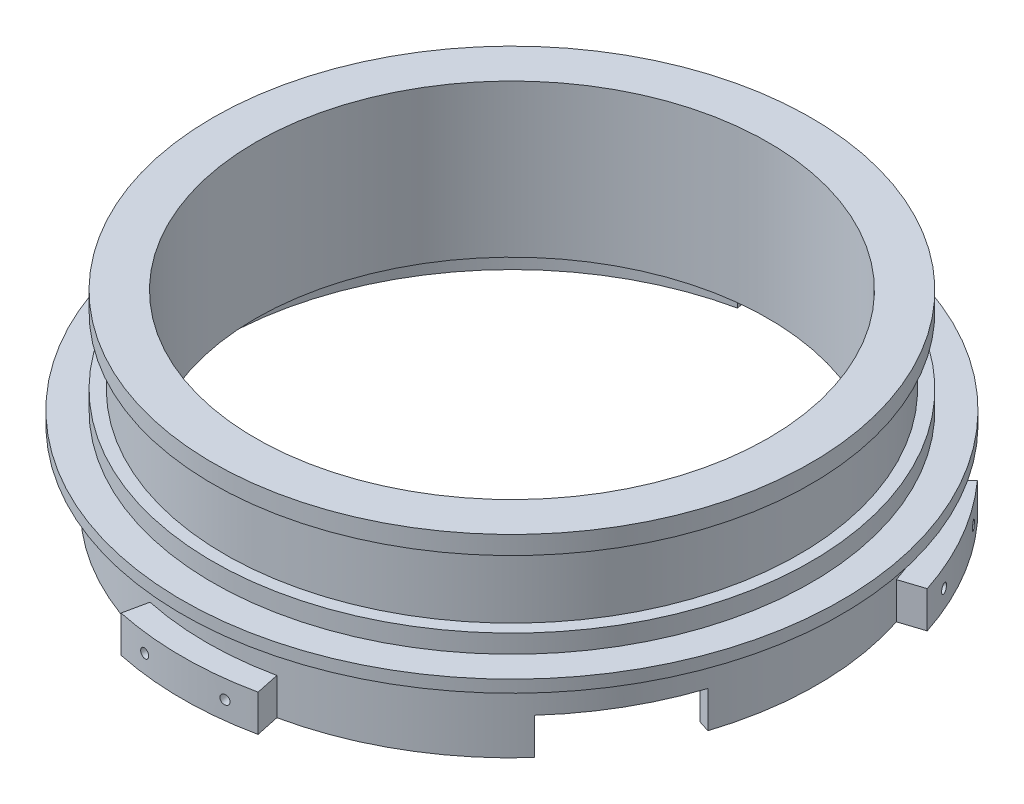
SolidWorks part; units mm, degrees
ref_plane "Front Plane" through (0, 0, 0) normal (0, 0, 1) x (1, 0, 0)
ref_plane "Top Plane" through (0, 0, 0) normal (0, 1, 0) x (1, 0, 0)
ref_plane "Right Plane" through (0, 0, 0) normal (1, 0, 0) x (0, 0, -1)
sketch "Sketch1" plane through (0, 0, 0) normal (0, 0, 1) x (1, 0, 0)
  line L0 (-42, 31) -> (-42, 6)
  line L1 (-42, 6) -> (-43, 6)
  line L2 (-43, 6) -> (-44, 7)
  line L3 (-44, 7) -> (-44, 10)
  line L4 (-44, 10) -> (-48, 10)
  line L5 (-48, 10) -> (-48, 0)
  line L6 (-48, 0) -> (-50, 0)
  line L7 (-50, 0) -> (-50, 12)
  line L8 (-50, 12) -> (-54, 12)
  line L9 (-54, 12) -> (-54, 14)
  line L10 (-54, 14) -> (-49, 14)
  line L11 (-49, 14) -> (-49, 17)
  line L12 (-49, 17) -> (-47, 17)
  line L13 (-47, 17) -> (-47, 28)
  line L14 (-47, 28) -> (-49, 28)
  line L15 (-49, 28) -> (-49, 31)
  line L16 (-49, 31) -> (-42, 31)
  line L17 (0, 15.8556) -> (0, -8.6801)
  dimension "D1" = 25
  dimension "D3" = 3
  dimension "D4" = 11
  dimension "D5" = 3
  dimension "D6" = 2
  dimension "D7" = 10
  dimension "D8" = 2
  dimension "D9" = 4
  dimension "D10" = 90
  dimension "D11" = 7
  dimension "D12" = 2
  dimension "D13" = 2
  dimension "D14" = 4
  dimension "D15" = 5
  dimension "D16" = 2
  dimension "D17" = 1
  dimension "D18" = 3
  dimension "D19" = 4
  dimension "D20" = 42
  dimension "D21" = 0
  dimension "D22" = 0
  dimension "D23" = 12
revolve "Revolve1" add sketch "Sketch1" angle 360 about L17 region at (-45.8886, 17.2118, 0)
sketch "Sketch2" plane through (0, 0, 0) normal (0, -1, 0) x (1, 0, 0)
  line L0 (0, 0) -> (0, 50)
  line L1 (0, 0) -> (-10.3956, 48.9074)
  line L2 (0, 0) -> (10.3956, 48.9074)
  line L3 (0, 0) -> (10.3956, -48.9074)
  line L4 (0, 0) -> (-10.3956, -48.9074)
  line L5 (0, 0) -> (-37.1572, 33.4565)
  line L6 (0, 0) -> (-47.5528, 15.4508)
  line L7 (0, 0) -> (37.1572, 33.4565)
  line L8 (0, 0) -> (47.5528, 15.4508)
  line L9 (0, 0) -> (37.1572, -33.4565)
  line L10 (0, 0) -> (47.5528, -15.4508)
  line L11 (0, 0) -> (-37.1572, -33.4565)
  line L12 (0, 0) -> (-47.5528, -15.4508)
  line L19 (0, 0) -> (40.1298, -36.1331)
  line L20 (0, 0) -> (51.3571, -16.6869)
  line L21 (0, 0) -> (11.2272, 52.82)
  line L22 (0, 0) -> (-11.2272, 52.82)
  line L23 (0, 0) -> (-40.1298, -36.1331)
  line L24 (0, 0) -> (-51.3571, -16.6869)
  circle A0 centre (0, 0) radius 50 construction
  arc A1 (11.2272, 52.82) -> (-11.2272, 52.82) centre (0, 0) ccw
  arc A2 (40.1298, -36.1331) -> (51.3571, -16.6869) centre (0, 0) ccw
  arc A3 (-51.3571, -16.6869) -> (-40.1298, -36.1331) centre (0, 0) ccw
  circle M1 centre (0, 0) radius 50
  circle M2 centre (0, 0) radius 48
  dimension "D20" = 108
  dimension "D1" = 24
  dimension "D2" = 12
  dimension "D3" = 24
  dimension "D4" = 24
  dimension "D5" = 24
  dimension "D6" = 36
  dimension "D7" = 24
  dimension "D8" = 36
  dimension "D9" = 36
  dimension "D10" = 24
  dimension "D11" = 36
  dimension "D12" = 36
  dimension "D13" = 36
  dimension "D21" = 24
  dimension "D22" = 0
  dimension "D23" = 24
  dimension "D24" = 0
  dimension "D25" = 24
  dimension "D26" = 0
extrude "Cut-Extrude1" cut sketch "Sketch2" against normal blind 6 contours L4 L3 M2 M1 region at (0, 0, -48.6493)
extrude "Cut-Extrude2" cut sketch "Sketch2<5>" against normal blind 6 contours L6 L5 M2 M1 region at (-42.1315, 0, 24.3247)
sketch "Sketch2<5>" plane through (0, 0, 0) normal (0, -1, 0) x (1, 0, 0) same geometry as "Sketch2"
extrude "Cut-Extrude3" cut sketch "Sketch2<6>" against normal blind 6 contours L8 L7 M2 M1 region at (42.1315, 0, 24.3247)
sketch "Sketch2<6>" plane through (0, 0, 0) normal (0, -1, 0) x (1, 0, 0) same geometry as "Sketch2"
extrude "Boss-Extrude1" add sketch "Sketch2<7>" against normal blind 6 contours L19 A2 L20 M1 region at (44.7269, 0, -25.8231)
sketch "Sketch2<7>" plane through (0, 0, 0) normal (0, -1, 0) x (1, 0, 0) same geometry as "Sketch2"
extrude "Boss-Extrude2" add sketch "Sketch2<8>" against normal blind 6 contours L21 A1 L22 M1 region at (0, 0, 51.6461)
sketch "Sketch2<8>" plane through (0, 0, 0) normal (0, -1, 0) x (1, 0, 0) same geometry as "Sketch2"
extrude "Boss-Extrude3" add sketch "Sketch2<9>" against normal blind 6 contours L24 A3 L23 M1 region at (-44.7269, 0, -25.8231)
sketch "Sketch2<9>" plane through (0, 0, 0) normal (0, -1, 0) x (1, 0, 0) same geometry as "Sketch2"
hole_wizard "Ø1.5mm Dowel Hole1" positions "3DSketch1" profile "Sketch3" hole size "Ø1.5" standard "ANSI Metric"
sketch3d "3DSketch1"
  line L0 (0, 0, 0) -> (0, 3, 0)
  line L2 (0, 3, 0) -> (6.5773, 3, 53.5979)
  line L4 (0, 3, 0) -> (-6.5846, 3, 53.597)
  line L6 (0, 3, 0) -> (49.7087, 3, -21.0961)
  line L8 (0, 3, 0) -> (43.1285, 3, -32.495)
  line L10 (0, 3, 0) -> (-49.7058, 3, -21.1029)
  line L12 (0, 3, 0) -> (-43.1241, 3, -32.501)
  line L18 (43.2996, 6, 25.003) -> (43.2996, 5, 25.003)
  line L22 (43.2996, 5, 25.003) -> (43.2996, 4, 25.003)
  line L26 (43.2996, 4, 25.003) -> (43.2996, 3, 25.003)
  line L28 (43.2996, 3, 25.003) -> (0, 3, 0)
  arc A1 (47.5528, 6, 15.4508) -> (37.1572, 6, 33.4565) centre (0, 6, 0) ccw construction
  point P0 (6.5773, 3, 53.5979)
  point P2 (-6.5846, 3, 53.597)
  point P4 (-49.7058, 3, -21.1029)
  point P6 (-43.1241, 3, -32.501)
  point P8 (43.1285, 3, -32.495)
  point P10 (49.7087, 3, -21.0961)
  point P47 (0, -44, 0)
  dimension "D1" = 3
  dimension "D2" = 3
  dimension "D3" = 3
  dimension "D4" = 3
  dimension "D5" = 3
  dimension "D6" = 3
  dimension "D7" = 3
  dimension "D8" = 14
  dimension "D9" = 14
  dimension "D10" = 14
  dimension "D11" = 106
  dimension "D14" = 1
  dimension "D12" = 1
  dimension "D13" = 106
  dimension "D15" = 1
  dimension "D16" = 53
  dimension "D17" = 53
sketch "Sketch3" plane through (6.5773, 3, 53.5979) normal (0, 1, 0) x (0.9926, 0, -0.1218)
  line L0 (0, 0) -> (0, 3.4506)
  line L1 (0, 3.4506) -> (0.75, 3)
  line L2 (0.75, 3) -> (0.75, 0)
  line L5 (0.75, 0) -> (0, 0)
  line L10 (0, 3.4506) -> (-0.75, 3) construction
  line L11 (0, -6.35) -> (0, 107.95) construction
  dimension "Hole Dia." = 1.5
  dimension "Hole Depth" = 3
  dimension "Drill Angle" = 118
